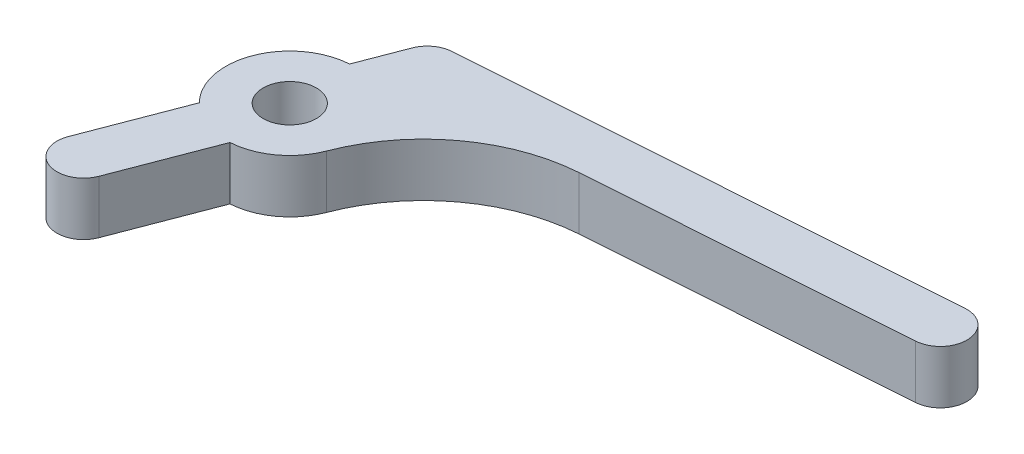
SolidWorks part; units mm, degrees
ref_plane "Front Plane" through (0, 0, 0) normal (0, 0, 1) x (1, 0, 0)
ref_plane "Top Plane" through (0, 0, 0) normal (0, 1, 0) x (1, 0, 0)
ref_plane "Right Plane" through (0, 0, 0) normal (1, 0, 0) x (0, 0, -1)
sketch "Sketch1" plane through (0, 0, 0) normal (0, 1, 0) x (1, 0, 0)
  line L0 (0, 0) -> (-6.8061, -17.7927) construction
  line L1 (2.9654, -1.1343) -> (-3.8406, -18.927)
  line L2 (-2.9654, 1.1343) -> (-9.7715, -16.6583)
  line L3 (0, 0) -> (4.5374, 11.8618) construction
  line L4 (-2.9654, 1.1343) -> (1.5719, 12.9961)
  line L5 (2.9654, -1.1343) -> (7.5028, 10.7274)
  line L6 (4.5374, 11.8618) -> (61.6874, 15.9254) construction
  line L7 (4.3122, 15.0288) -> (61.4622, 19.0924)
  line L8 (4.7626, 8.6948) -> (61.9126, 12.7584)
  line L9 (7.1328, -2.7285) -> (0, 0) construction
  circle A0 centre (0, 0) radius 2.7781 construction
  arc A1 (2.9654, -1.1343) -> (-2.9654, 1.1343) centre (0, 0) ccw
  arc A2 (-9.7715, -16.6583) -> (-3.8406, -18.927) centre (-6.8061, -17.7927) ccw
  arc A3 (-2.9654, 1.1343) -> (2.9654, -1.1343) centre (0, 0) ccw
  arc A4 (7.5028, 10.7274) -> (1.5719, 12.9961) centre (4.5374, 11.8618) ccw
  arc A5 (4.3122, 15.0288) -> (4.7626, 8.6948) centre (4.5374, 11.8618) ccw
  arc A6 (61.9126, 12.7584) -> (61.4622, 19.0924) centre (61.6874, 15.9254) ccw
  circle A7 centre (0, 0) radius 7.6369
  arc A8 (7.1328, -2.7285) -> (24.4167, 10.0923) centre (25.837, -9.8832) cw
  point P4 (-3.403, -8.8963)
  point P11 (2.2687, 5.9309)
  point P16 (33.1124, 13.8936)
  dimension "D1" = 5.5562
  dimension "D2" = 3.175
  dimension "D3" = 12.7
  dimension "D4" = 19.05
  dimension "D5" = 115
  dimension "D6" = 57.15
extrude "Boss-Extrude1" add sketch "Sketch1" along normal blind 6.35 contours L4 A7 L2 | L5 A7 L4 A1 | L2 A7 L1 A3 | L1 A7 L5 | A7 L5 L8 A5 L4 | L8 A6 L7 A4 L5 | A7 A8 L8 L5 | A4 A5 L8 L5 | A7 L2 A2 L1 region at (4.6828, 0, 1.7913) region at (1.7526, 0, -4.5816) region at (-1.7526, 0, 4.5816) region at (-5.1782, 0, 13.5369) region at (3.039, 0, -8.2668) region at (10.8007, 0, -6.1955) region at (-4.6828, 0, -1.7913) region at (4.5802, 0, -11.8041) region at (35.6561, 0, -14.0799)
